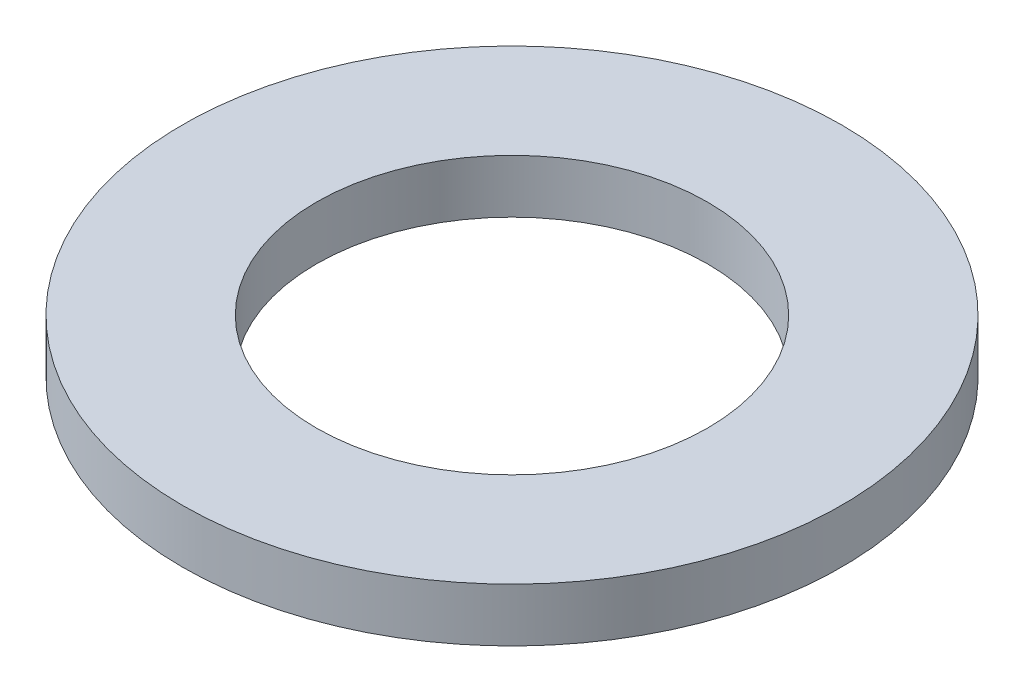
SolidWorks part; units mm, degrees
ref_plane "Front Plane" through (0, 0, 0) normal (0, 0, 1) x (1, 0, 0)
ref_plane "Top Plane" through (0, 0, 0) normal (0, 1, 0) x (1, 0, 0)
ref_plane "Right Plane" through (0, 0, 0) normal (1, 0, 0) x (0, 0, -1)
sketch "Sketch1" plane through (0, 0, 0) normal (0, 1, 0) x (1, 0, 0)
  circle A0 centre (0, 0) radius 80
  dimension "FLANGE_OD" = 160
extrude "Boss-Extrude1" add sketch "Sketch1" along normal blind 13
sketch "Sketch2" plane through (0, 0, 0) normal (0, 1, 0) x (1, 0, 0)
  circle A0 centre (0, 0) radius 47.5
  dimension "BORE_D" = 95
extrude "Cut-Extrude1" cut sketch "Sketch2" along normal through all
sketch "Sketch3" plane through (0, 13, 0) normal (0, 1, 0) x (1, 0, 0)
  circle A0 centre (0, 0) radius 34.6311 construction
  circle A1 centre (-34.6311, 0) radius 5.5542
  dimension "BOLT_D" = 11.1084
  dimension "BOLT_PCD" = 69.2621
extrude "Cut-Extrude2" cut sketch "Sketch3" against normal blind 8.8486 rebuild error yes
pattern_circular "CirPattern1" count 8 over 360 rebuild error yes
